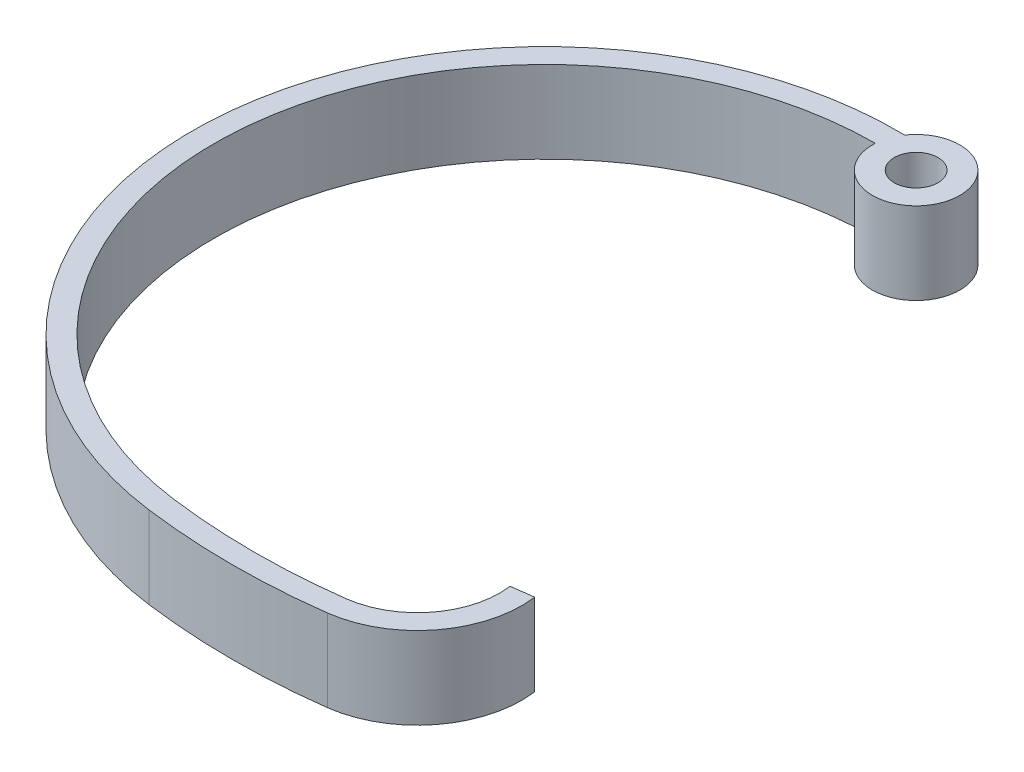
SolidWorks part; units mm, degrees
ref_plane "Plan de face" through (0, 0, 0) normal (0, 0, 1) x (1, 0, 0)
ref_plane "Plan de dessus" through (0, 0, 0) normal (0, 1, 0) x (1, 0, 0)
ref_plane "Plan de droite" through (0, 0, 0) normal (1, 0, 0) x (0, 0, -1)
sketch "Esquisse1" plane through (0, 0, 0) normal (0, 1, 0) x (1, 0, 0)
  line L0 (0, 0) -> (15.7558, -119.9698) construction
  line L1 (0, 0) -> (-15.7937, -119.9648) construction
  line L2 (7.8779, -59.9849) -> (15.7558, -119.9698) construction
  line L3 (7.8779, -59.9849) -> (15.7558, -119.9698) construction
  line L4 (11.8169, -89.9774) -> (15.7558, -119.9698) construction
  line L5 (11.8169, -89.9774) -> (15.7558, -119.9698) construction
  line L6 (13.7864, -104.9736) -> (28.7826, -103.0041) construction
  line L9 (4.4717, 3.3206) -> (2.8843, -8.7366) construction
  line L10 (0, 0) -> (-1.0815, -8.2145) construction
  line L11 (28.7826, -103.0041) -> (32.7485, -102.4832)
  arc A0 (16.2767, -123.9357) -> (32.7485, -102.4832) centre (13.7864, -104.9736) ccw
  arc A1 (15.7558, -119.9698) -> (28.7826, -103.0041) centre (13.7864, -104.9736) ccw
  arc A2 (15.7558, -119.9698) -> (-15.7937, -119.9648) centre (0, 0) ccw construction
  arc A3 (-15.7937, -119.9648) -> (15.7558, -119.9698) centre (0, 0) ccw
  arc A4 (-15.7937, -119.9648) -> (-7.9832, 0.5175) centre (-7.8968, -59.9824) cw
  arc A5 (-16.3158, -123.9306) -> (16.2767, -123.9357) centre (0, 0) ccw
  arc A6 (-16.3158, -123.9306) -> (-6.6111, 4.5048) centre (-7.8968, -59.9824) cw
  circle A7 centre (0, 0) radius 4
  arc A8 (-16.3158, -123.9306) -> (4.4717, 3.3206) centre (-7.8968, -59.9824) cw construction
  arc A9 (-7.9832, 0.5175) -> (-6.6111, 4.5048) centre (0, 0) ccw
  arc A11 (-15.7937, -119.9648) -> (0, 0) centre (-7.8968, -59.9824) cw construction
  dimension "D1" = 4
extrude "Boss.-Extru.3" add sketch "Esquisse1" along normal blind 15
hole_wizard "Trou taraudé M3x0.51" positions "Esquisse8" profile "Esquisse7" tap size "M3x0.5" standard "Ansi Métrique" end condition through all
sketch "Esquisse8" plane through (0, 0, 0) normal (0, 0, 1) x (1, 0, 0)
  line L0 (16.2767, 15) -> (-16.3158, 15) construction
  line L1 (-4, 15) -> (-4, 0) construction
  point P0 (-1, 7.5)
  point P2 (-0.0195, 15)
  dimension "D1" = 7.5
  dimension "D2" = 3
sketch "Esquisse7" plane through (-1, 7.5, 0) normal (1, 0, 0) x (0, -1, 0)
  line L0 (0, 0) -> (0, 8)
  line L1 (0, 8) -> (1.25, 8)
  line L2 (1.25, 8) -> (1.25, 0)
  line L5 (1.25, 0) -> (0, 0)
  line L11 (0, -6.35) -> (0, 107.95) construction
  dimension "Diamètre du trou pour taraudage jusqu'au prochain" = 2.5
  dimension "Profondeur du trou pour taraudage jusqu'au prochain" = 8
cosmetic thread "Filetage de perçage1" parameters "D1"=0, "D2"=3.5
